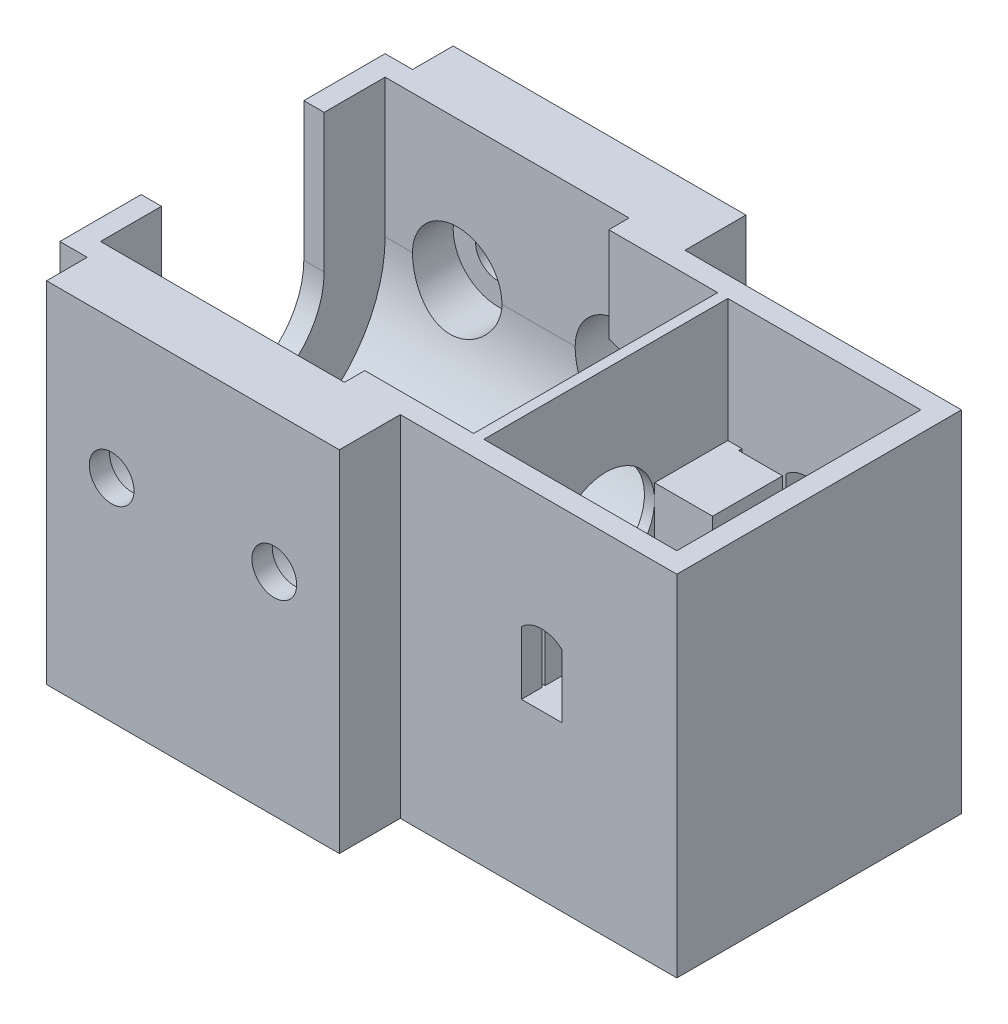
SolidWorks part; units mm, degrees
ref_plane "Front Plane" through (0, 0, 0) normal (0, 0, 1) x (1, 0, 0)
ref_plane "Top Plane" through (0, 0, 0) normal (0, 1, 0) x (1, 0, 0)
ref_plane "Right Plane" through (0, 0, 0) normal (1, 0, 0) x (0, 0, -1)
sketch "Sketch1" plane through (0, 0, 0) normal (0, 0, 1) x (1, 0, 0)
  line L1 (-76.2, -50.8) -> (40.64, -50.8)
  line L2 (-76.2, -50.8) -> (-76.2, 0)
  line L3 (-76.2, 0) -> (40.64, 0)
  line L4 (40.64, -50.8) -> (40.64, 0)
  line L5 (-76.2, -50.8) -> (40.64, 0) construction
  line L6 (-76.2, 0) -> (40.64, -50.8) construction
  point P0 (0, 0)
  dimension "D1" = 116.84
  dimension "D2" = 50.8
  dimension "D3" = 76.2
extrude "Boss-Extrude1" add sketch "Sketch1" along normal mid plane 63.5
sketch "Sketch2" plane through (0, 0, 0) normal (0, 0, 1) x (1, 0, 0)
  line L0 (-152.4829, -25.4) -> (6.8382, -25.4) construction
  line L1 (-49.3609, -3.175) -> (-49.3609, -12.7)
  line L2 (40.64, 0) -> (-76.2, 0) construction
  line L3 (40.64, 0) -> (-76.2, 0) construction
  line L4 (-11.2609, -3.175) -> (-11.2609, -6.35)
  line L5 (-11.2609, -25.4) -> (-11.2609, -3.175) construction
  line L6 (-128.4172, -25.4) -> (-157.8092, -25.4)
  line L7 (6.8382, -25.4) -> (40.64, -25.4)
  line L8 (-607.3619, -25.4) -> (6.8382, -25.4) construction
  line L9 (-49.3609, -3.175) -> (-11.2609, -3.175)
  line L10 (6.8382, -25.4) -> (-128.4172, -25.4)
  line L11 (-11.2609, -6.35) -> (5.7391, -6.35)
  line L12 (5.7391, -6.35) -> (5.7391, -17.78)
  line L13 (5.7391, -17.78) -> (23.7391, -17.78)
  line L14 (-49.3609, -12.7) -> (-220.2024, -12.7)
  line L15 (-220.2024, -12.7) -> (-220.2024, -25.4)
  line L16 (-220.2024, -25.4) -> (-157.8092, -25.4)
  line L17 (23.7391, -17.78) -> (23.7391, -25.4) construction
  line L18 (23.7391, -17.78) -> (40.64, -17.78)
  line L19 (40.64, -50.8) -> (40.64, 0) construction
  line L20 (40.64, -17.78) -> (40.64, -25.4)
  line L21 (-76.2, 0) -> (-76.2, -50.8) construction
  point P23 (-11.2609, -25.4)
  dimension "D1" = 22.225
  dimension "D2" = 38.1
  dimension "D3" = 25.4
  dimension "D4" = 35
  dimension "D5" = 7.62
  dimension "D6" = 3.175
  dimension "D7" = 26.8391
  dimension "D8" = 18
  dimension "D9" = 12.7
revolve "Cut-Revolve1" cut sketch "Sketch2" angle 360 about L0
sketch "Sketch38" plane through (40.64, 0, 0) normal (1, 0, 0) x (0, 0, -1)
  line L1 (-10, -35.4) -> (10, -35.4)
  line L2 (-10, -35.4) -> (-10, -15.4)
  line L3 (-10, -15.4) -> (10, -15.4)
  line L4 (10, -35.4) -> (10, -15.4)
  line L5 (-10, -35.4) -> (10, -15.4) construction
  line L6 (-10, -15.4) -> (10, -35.4) construction
  point P0 (0, -25.4)
  point P1 (0, -25.4)
  dimension "D1" = 20
  dimension "D2" = 20
extrude "Cut-Extrude33" cut sketch "Sketch38" against normal offset from surface (33.3134 mm away) 1.5875 up to face at (5.7391, -44.45, 0)
sketch "Sketch37" plane through (40.64, 0, 0) normal (1, 0, 0) x (0, 0, -1)
  line L0 (31.75, -50.8) -> (31.75, 0) construction
  line L1 (-31.75, 0) -> (31.75, 0)
  line L2 (-31.75, 0) -> (-31.75, -25.4)
  line L3 (-31.75, -25.4) -> (31.75, -25.4)
  line L4 (31.75, 0) -> (31.75, -25.4)
  line L5 (10, -35.4) -> (10, -15.4) construction
  point P7 (0, -25.4)
  point P11 (0, 0)
  point P14 (10, -25.4)
extrude "Cut-Extrude32" cut sketch "Sketch37" against normal through all
sketch "Sketch39" plane through (0, -25.4, 0) normal (0, 1, 0) x (1, 0, 0)
  line L10 (-76.2, 12.7) -> (-49.3609, 12.7)
  line L11 (-49.3609, 12.7) -> (-49.3609, 22.225)
  line L12 (-49.3609, 22.225) -> (-11.2609, 22.225)
  line L13 (-11.2609, 22.225) -> (-11.2609, 19.05)
  line L14 (-11.2609, 19.05) -> (5.7391, 19.05)
  line L15 (5.7391, 19.05) -> (5.7391, 7.62)
  line L16 (5.7391, 19.05) -> (5.7391, 7.62)
  line L17 (40.64, 10) -> (40.64, 31.75)
  line L18 (40.64, 31.75) -> (-76.2, 31.75)
  line L19 (-76.2, 31.75) -> (-76.2, 12.7)
  line L20 (-76.2, 12.7) -> (-49.3609, 12.7)
  line L21 (-49.3609, 12.7) -> (-49.3609, 22.225)
  line L22 (-49.3609, 22.225) -> (-11.2609, 22.225)
  line L23 (-11.2609, 22.225) -> (-11.2609, 19.05)
  line L24 (-11.2609, 19.05) -> (5.7391, 19.05)
  line L25 (7.3266, 10) -> (40.64, 10)
  line L26 (7.3266, 10) -> (40.64, 10)
  line L27 (40.64, 10) -> (40.64, 31.75)
  line L28 (40.64, 31.75) -> (-76.2, 31.75)
  line L29 (-76.2, 31.75) -> (-76.2, 12.7)
  line L30 (-49.3609, -12.7) -> (-76.2, -12.7)
  line L31 (-76.2, -12.7) -> (-76.2, -31.75)
  line L32 (-76.2, -31.75) -> (40.64, -31.75)
  line L33 (40.64, -31.75) -> (40.64, -10)
  line L34 (40.64, -10) -> (7.3266, -10)
  line L35 (40.64, -10) -> (7.3266, -10)
  line L36 (5.7391, -19.05) -> (-11.2609, -19.05)
  line L37 (-11.2609, -19.05) -> (-11.2609, -22.225)
  line L38 (-11.2609, -22.225) -> (-49.3609, -22.225)
  line L39 (-49.3609, -22.225) -> (-49.3609, -12.7)
  line L40 (-49.3609, -12.7) -> (-76.2, -12.7)
  line L41 (-76.2, -12.7) -> (-76.2, -31.75)
  line L42 (-76.2, -31.75) -> (40.64, -31.75)
  line L43 (40.64, -31.75) -> (40.64, -10)
  line L44 (5.7391, -7.62) -> (5.7391, -19.05)
  line L45 (5.7391, -7.62) -> (5.7391, -19.05)
  line L46 (5.7391, -19.05) -> (-11.2609, -19.05)
  line L47 (-11.2609, -19.05) -> (-11.2609, -22.225)
  line L48 (-11.2609, -22.225) -> (-49.3609, -22.225)
  line L49 (-49.3609, -22.225) -> (-49.3609, -12.7)
  line L52 (5.7391, 7.62) -> (7.3266, 7.62)
  line L53 (5.7391, 7.62) -> (7.3266, 7.62)
  line L54 (7.3266, 7.62) -> (7.3266, 10)
  line L55 (7.3266, 7.62) -> (7.3266, 10)
  line L56 (7.3266, -10) -> (7.3266, -7.62)
  line L57 (7.3266, -10) -> (7.3266, -7.62)
  line L58 (7.3266, -7.62) -> (5.7391, -7.62)
  line L59 (7.3266, -7.62) -> (5.7391, -7.62)
  dimension "D1" = 0
  dimension "D2" = 0
extrude "Boss-Extrude5" add sketch "Sketch39" along normal blind 25.4
sketch "Sketch40" plane through (0, 0, 0) normal (0, 1, 0) x (1, 0, 0)
  line L0 (7.3266, 10) -> (40.64, 10) construction
  line L1 (23.7391, 10) -> (40.64, 10)
  line L2 (23.7391, 10) -> (23.7391, -10)
  line L3 (23.7391, -10) -> (40.64, -10)
  line L4 (40.64, 10) -> (40.64, -10)
  line L6 (-11.2609, 22.225) -> (-11.2609, 19.05) construction
  dimension "D1" = 35
extrude "Boss-Extrude6" add sketch "Sketch40" against normal up to next
sketch "Sketch41" plane through (0, 0, 0) normal (0, 1, 0) x (1, 0, 0)
  line L2 (-76.2, 12.7) -> (-76.2, -12.7) construction
  circle A0 centre (-57.15, 0) radius 3.1134
  circle A1 centre (-31.75, 0) radius 3.1134
  circle A2 centre (-6.35, 0) radius 3.1134
  dimension "D1" = 19.05
extrude "Cut-Extrude34" cut sketch "Sketch41" against normal through all
ref_plane "Plane_Mid" through (0, -25.4, 0) normal (0, 1, 0) x (1, 0, 0)
ref_axis "Axis1" through (7.3266, -25.4, 0) along (-1, 0, 0)
sketch "Sketch42" plane through (0, 0, 0) normal (0, 0, 1) x (1, 0, 0)
  line L0 (1.7462, -25.4) -> (-1.7462, -25.4) construction
  line L1 (-76.2, 0) -> (-76.2, -25.4) construction
  circle A0 centre (-38.1, -25.4) radius 3.4925
  circle A1 centre (-12.7, -25.4) radius 3.4925
  dimension "D1" = 6.985
  dimension "D2" = 38.1
extrude "Cut-Extrude35" cut sketch "Sketch42" against normal through all both and the other way through all
sketch "Sketch43" plane through (0, 0, 0) normal (0, 0, 1) x (1, 0, 0)
  circle A0 centre (-38.1, -25.4) radius 6.985
  circle A1 centre (-12.7, -25.4) radius 6.985
  dimension "D1" = 13.97
extrude "Cut-Extrude36" cut sketch "Sketch43" against normal offset from surface (28.575 mm away) 3.175 up to face at (-9.2075, -25.4, -31.75)
extrude "Cut-Extrude37" cut sketch "Sketch43<2>" along normal offset from surface (28.575 mm away) 3.175 up to face at (-9.2075, -25.4, 31.75)
sketch "Sketch43<2>" plane through (0, 0, 0) normal (0, 0, 1) x (1, 0, 0) same geometry as "Sketch43"
sketch "Sketch44" plane through (0, 0, 0) normal (0, 1, 0) x (1, 0, 0)
  line L0 (5.7391, -19.05) -> (-11.2609, -19.05) construction
  line L1 (7.3266, 19.05) -> (23.2391, 19.05)
  line L2 (7.3266, 19.05) -> (7.3266, -19.05)
  line L3 (7.3266, -19.05) -> (23.2391, -19.05)
  line L4 (23.2391, 19.05) -> (23.2391, -19.05)
  line L5 (-11.2609, 19.05) -> (5.7391, 19.05) construction
  line L6 (7.3266, 7.62) -> (7.3266, 10) construction
  line L7 (23.7391, 10) -> (23.7391, -10) construction
  dimension "D1" = 0.5
extrude "Cut-Extrude38" cut sketch "Sketch44" against normal up to surface (35.4 mm away) up to face at (15.5329, -35.4, 0)
sketch "Sketch45" plane through (0, 0, 0) normal (0, 0, 1) x (1, 0, 0)
  line L0 (40.64, 0) -> (-76.2, 0) construction
  line L2 (37.465, 0) -> (23.2391, 0)
  line L4 (37.465, 0) -> (37.465, -15.4)
  line L5 (37.465, -15.4) -> (23.2391, -15.4)
  line L8 (23.2391, 0) -> (23.2391, -15.4)
  line L9 (40.64, -50.8) -> (40.64, 0) construction
  line L10 (23.2391, -35.4) -> (23.2391, 0) construction
  line L11 (-5.715, -25.4) -> (5.7391, -25.4) construction
  dimension "D1" = 3.175
  dimension "D2" = 10
extrude "Cut-Extrude39" cut sketch "Sketch45" against normal up to surface and the other way up to surface up to face at (15.2828, -17.7, -19.05) other way up to face at (15.2828, -17.7, 19.05)
sketch "Sketch46" plane through (0, 0, 0) normal (0, 1, 0) x (1, 0, 0)
  line L0 (-11.2609, 19.05) -> (5.7391, 19.05) construction
  line L1 (40.64, 31.75) -> (-2.54, 31.75)
  line L2 (40.64, 31.75) -> (40.64, 22.225)
  line L3 (40.64, 22.225) -> (-2.54, 22.225)
  line L4 (-2.54, 31.75) -> (-2.54, 22.225)
  line L5 (-76.2, 0) -> (40.64, 0) construction
  line L6 (-76.2, 12.7) -> (-76.2, -12.7) construction
  line L7 (40.64, -31.75) -> (40.64, 31.75) construction
  line L8 (40.64, -31.75) -> (40.64, -22.225)
  line L9 (40.64, -22.225) -> (-2.54, -22.225)
  line L10 (40.64, -31.75) -> (-2.54, -31.75)
  line L11 (-2.54, -31.75) -> (-2.54, -22.225)
  line L12 (-49.3609, 22.225) -> (-11.2609, 22.225) construction
  line L13 (-76.2, 31.75) -> (-48.26, 31.75)
  line L14 (-76.2, 31.75) -> (-76.2, 25.4)
  line L15 (-76.2, 25.4) -> (-48.26, 25.4)
  line L16 (-48.26, 31.75) -> (-48.26, 25.4)
  line L17 (-48.26, -31.75) -> (-48.26, -25.4)
  line L18 (-76.2, -25.4) -> (-48.26, -25.4)
  line L19 (-76.2, -31.75) -> (-76.2, -25.4)
  line L20 (-76.2, -31.75) -> (-48.26, -31.75)
  dimension "D1" = 3.175
  dimension "D2" = 3.175
  dimension "D3" = 3.175
  dimension "D4" = 3.175
extrude "Cut-Extrude40" cut sketch "Sketch46" against normal through all
sketch "Sketch49" plane through (0, 0, 0) normal (0, 1, 0) x (1, 0, 0)
  line L0 (-48.26, -25.4) -> (-76.2, -25.4) construction
  line L1 (-76.2, 25.4) -> (-52.5359, 25.4)
  line L2 (-76.2, 25.4) -> (-76.2, -25.4)
  line L3 (-76.2, -25.4) -> (-52.5359, -25.4)
  line L4 (-52.5359, 25.4) -> (-52.5359, -25.4)
  line L5 (-49.3609, -22.225) -> (-49.3609, 22.225) construction
  dimension "D1" = 3.175
extrude "Cut-Extrude42" cut sketch "Sketch49" against normal through all
sketch "Sketch50" plane through (0, 0, 0) normal (0, 1, 0) x (1, 0, 0)
  line L0 (-2.54, 22.225) -> (40.64, 22.225) construction
  line L1 (22.9851, 20.701) -> (23.2391, 20.701)
  line L2 (22.9851, 20.701) -> (22.9851, 22.225)
  line L3 (22.9851, 22.225) -> (23.2391, 22.225)
  line L4 (23.2391, 20.701) -> (23.2391, 22.225)
  line L5 (23.1121, 22.225) -> (23.1121, 20.701) construction
  line L6 (22.9851, 21.463) -> (23.2391, 21.463) construction
  line L8 (23.2391, 10) -> (23.2391, 19.05) construction
  line L9 (21.4611, 20.701) -> (21.7151, 20.701)
  line L10 (21.7151, 20.701) -> (21.7151, 22.225)
  line L11 (21.4611, 22.225) -> (21.7151, 22.225)
  line L12 (21.4611, 20.701) -> (21.4611, 22.225)
  line L13 (19.9371, 20.701) -> (20.1911, 20.701)
  line L14 (20.1911, 20.701) -> (20.1911, 22.225)
  line L15 (19.9371, 22.225) -> (20.1911, 22.225)
  line L16 (19.9371, 20.701) -> (19.9371, 22.225)
  line L17 (18.4131, 20.701) -> (18.6671, 20.701)
  line L18 (18.6671, 20.701) -> (18.6671, 22.225)
  line L19 (18.4131, 22.225) -> (18.6671, 22.225)
  line L20 (18.4131, 20.701) -> (18.4131, 22.225)
  line L21 (16.8891, 20.701) -> (17.1431, 20.701)
  line L22 (17.1431, 20.701) -> (17.1431, 22.225)
  line L23 (16.8891, 22.225) -> (17.1431, 22.225)
  line L24 (16.8891, 20.701) -> (16.8891, 22.225)
  line L25 (15.3651, 20.701) -> (15.6191, 20.701)
  line L26 (15.6191, 20.701) -> (15.6191, 22.225)
  line L27 (15.3651, 22.225) -> (15.6191, 22.225)
  line L28 (15.3651, 20.701) -> (15.3651, 22.225)
  line L29 (13.8411, 20.701) -> (14.0951, 20.701)
  line L30 (14.0951, 20.701) -> (14.0951, 22.225)
  line L31 (13.8411, 22.225) -> (14.0951, 22.225)
  line L32 (13.8411, 20.701) -> (13.8411, 22.225)
  line L33 (12.3171, 20.701) -> (12.5711, 20.701)
  line L34 (12.5711, 20.701) -> (12.5711, 22.225)
  line L35 (12.3171, 22.225) -> (12.5711, 22.225)
  line L36 (12.3171, 20.701) -> (12.3171, 22.225)
  line L37 (10.7931, 20.701) -> (11.0471, 20.701)
  line L38 (11.0471, 20.701) -> (11.0471, 22.225)
  line L39 (10.7931, 22.225) -> (11.0471, 22.225)
  line L40 (10.7931, 20.701) -> (10.7931, 22.225)
  line L41 (9.2691, 20.701) -> (9.5231, 20.701)
  line L42 (9.5231, 20.701) -> (9.5231, 22.225)
  line L43 (9.2691, 22.225) -> (9.5231, 22.225)
  line L44 (9.2691, 20.701) -> (9.2691, 22.225)
  point P0 (23.1121, 21.463)
  dimension "D1" = 0.254
  dimension "D2" = 1.524
  dimension "D3" = 10
extrude "Cut-Extrude43" cut sketch "Sketch50" against normal blind 2.54
sketch "Sketch52" plane through (23.7391, 0, 0) normal (-1, 0, 0) x (0, 0, 1)
  circle A0 centre (0, -25.4) radius 0.3175
  dimension "D1" = 0.635
extrude "Cut-Extrude45" cut sketch "Sketch52" against normal blind 0.0508
sketch "Sketch53" plane through (23.7391, 0, 0) normal (-1, 0, 0) x (0, 0, 1)
  circle A0 centre (0, -25.4) radius 2
  dimension "D1" = 4
extrude "Cut-Extrude46" cut sketch "Sketch53" against normal blind 0.0254
sketch "Sketch54" plane through (0, -35.4, 0) normal (0, 1, 0) x (1, 0, 0)
  line L0 (23.2391, 10) -> (23.2391, -10)
  line L8 (23.7391, 10) -> (23.2391, 10)
  line L9 (23.2391, 10) -> (23.2391, 19.05)
  line L10 (23.2391, 19.05) -> (7.3266, 19.05)
  line L11 (7.3266, 19.05) -> (7.3266, -19.05)
  line L12 (7.3266, -19.05) -> (23.2391, -19.05)
  line L13 (23.2391, -19.05) -> (23.2391, -10)
  line L14 (23.2391, -10) -> (23.7391, -10)
  line L15 (23.7391, -10) -> (23.7391, 10)
  line L17 (23.2391, 10) -> (23.2391, 19.05)
  line L18 (23.2391, 19.05) -> (7.3266, 19.05)
  line L19 (7.3266, 19.05) -> (7.3266, -19.05)
  line L20 (7.3266, -19.05) -> (23.2391, -19.05)
  line L21 (23.2391, -19.05) -> (23.2391, -10)
  dimension "D1" = 0
extrude "Boss-Extrude7" add sketch "Sketch54" along normal blind 2.54
sketch "Sketch55" plane through (0, -32.86, 0) normal (0, 1, 0) x (1, 0, 0)
  line L0 (23.2391, -19.05) -> (23.2391, -10) construction
  line L1 (23.2391, 10) -> (7.3266, 10)
  line L2 (23.2391, 10) -> (23.2391, 19.05)
  line L3 (23.2391, 19.05) -> (7.3266, 19.05)
  line L4 (7.3266, 10) -> (7.3266, 19.05)
  line L5 (23.2391, 10) -> (7.3266, 19.05) construction
  line L6 (23.2391, 19.05) -> (7.3266, 10) construction
  line L7 (7.3266, -19.05) -> (23.2391, -19.05)
  line L8 (7.3266, -19.05) -> (7.3266, -10)
  line L9 (7.3266, -10) -> (23.2391, -10)
  line L10 (23.2391, -19.05) -> (23.2391, -10)
  line L11 (7.3266, -19.05) -> (23.2391, -10) construction
  line L12 (7.3266, -10) -> (23.2391, -19.05) construction
  point P4 (15.2828, 14.525)
  point P11 (15.2828, -14.525)
extrude "Boss-Extrude8" add sketch "Sketch55" along normal up to surface (17.46 mm away) up to face at (26.9206, -15.4, 0)
sketch "Sketch57" plane through (0, -15.4, 0) normal (0, 1, 0) x (1, 0, 0)
  line L8 (23.7391, -10) -> (7.3266, -10)
  line L9 (7.3266, -10) -> (7.3266, -19.05)
  line L10 (7.3266, -19.05) -> (37.465, -19.05)
  line L11 (37.465, -19.05) -> (37.465, 19.05)
  line L12 (37.465, 19.05) -> (7.3266, 19.05)
  line L13 (23.7391, -10) -> (7.3266, -10)
  line L14 (7.3266, 19.05) -> (7.3266, 10)
  line L15 (23.7391, 10) -> (23.7391, -10)
  line L16 (7.3266, 19.05) -> (7.3266, 10)
  line L17 (7.3266, -10) -> (7.3266, -19.05)
  line L18 (7.3266, -19.05) -> (37.465, -19.05)
  line L19 (37.465, -19.05) -> (37.465, 19.05)
  line L20 (37.465, 19.05) -> (7.3266, 19.05)
  line L21 (7.3266, 10) -> (23.7391, 10)
  line L22 (7.3266, 10) -> (23.7391, 10)
  line L23 (23.7391, 10) -> (23.7391, -10)
  dimension "D1" = 0
extrude "Cut-Extrude47" cut sketch "Sketch57" against normal blind 7.62
sketch "Sketch58" plane through (0, -50.8, 0) normal (0, -1, 0) x (1, 0, 0)
  line L12 (-48.26, 25.4) -> (-52.5359, 25.4)
  line L13 (-52.5359, 25.4) -> (-52.5359, -25.4)
  line L14 (-52.5359, -25.4) -> (-48.26, -25.4)
  line L15 (-48.26, -25.4) -> (-48.26, -31.75)
  line L16 (-48.26, -31.75) -> (-2.54, -31.75)
  line L17 (-2.54, -31.75) -> (-2.54, -22.225)
  line L18 (-2.54, -22.225) -> (40.64, -22.225)
  line L19 (40.64, -22.225) -> (40.64, 22.225)
  line L20 (40.64, 22.225) -> (-2.54, 22.225)
  line L21 (-2.54, 22.225) -> (-2.54, 31.75)
  line L22 (-2.54, 31.75) -> (-48.26, 31.75)
  line L23 (-48.26, 31.75) -> (-48.26, 25.4)
  line L24 (-48.26, 25.4) -> (-52.5359, 25.4)
  line L25 (-52.5359, 25.4) -> (-52.5359, -25.4)
  line L26 (-52.5359, -25.4) -> (-48.26, -25.4)
  line L27 (-48.26, -25.4) -> (-48.26, -31.75)
  line L28 (-48.26, -31.75) -> (-2.54, -31.75)
  line L29 (-2.54, -31.75) -> (-2.54, -22.225)
  line L30 (-2.54, -22.225) -> (40.64, -22.225)
  line L31 (40.64, -22.225) -> (40.64, 22.225)
  line L32 (40.64, 22.225) -> (-2.54, 22.225)
  line L33 (-2.54, 22.225) -> (-2.54, 31.75)
  line L34 (-2.54, 31.75) -> (-48.26, 31.75)
  line L35 (-48.26, 31.75) -> (-48.26, 25.4)
  circle A0 centre (-31.75, 0) radius 3.1134
  circle A1 centre (-6.35, 0) radius 3.1134
  circle A2 centre (-6.35, 0) radius 3.1134 construction
  circle A3 centre (-31.75, 0) radius 3.1134 construction
  dimension "D1" = 0
extrude "Boss-Extrude10" add sketch "Sketch58" along normal blind 7.62
sketch "Sketch59" plane through (0, -35.4, 0) normal (0, 1, 0) x (1, 0, 0)
  line L4 (23.2391, 10) -> (23.2391, -10)
  line L5 (23.2391, -10) -> (23.7391, -10)
  line L6 (23.7391, -10) -> (23.7391, 10)
  line L7 (23.7391, 10) -> (23.2391, 10)
  line L8 (23.2391, 10) -> (23.2391, -10)
  line L9 (23.2391, -10) -> (23.7391, -10)
  line L10 (23.7391, -10) -> (23.7391, 10)
  line L11 (23.7391, 10) -> (23.2391, 10)
  dimension "D1" = 0
extrude "Cut-Extrude48" cut sketch "Sketch59" against normal blind 7.62
sketch "Sketch51" plane through (0, -23.02, 0) normal (0, 1, 0) x (1, 0, 0)
  line L0 (25.098, 0.254) -> (26.1082, 0.254)
  line L1 (24.59, 2.54) -> (25.098, 2.54)
  line L2 (24.59, 2.54) -> (24.59, 0.254)
  line L3 (24.59, -2.54) -> (25.098, -2.54)
  line L4 (25.098, 2.54) -> (25.098, 0.254)
  line L5 (29.6527, -0.254) -> (30.6629, -0.254)
  line L6 (25.098, -0.254) -> (25.098, -2.54)
  line L7 (26.6162, 2.54) -> (26.6162, 0.254)
  line L8 (26.1082, 2.54) -> (26.6162, 2.54)
  line L9 (26.1082, 2.54) -> (26.1082, 0.254)
  line L10 (26.1082, -2.54) -> (26.6162, -2.54)
  line L11 (28.1344, 2.54) -> (28.1344, 0.254)
  line L12 (27.6264, 2.54) -> (28.1344, 2.54)
  line L13 (27.6264, 2.54) -> (27.6264, 0.254)
  line L14 (27.6264, -2.54) -> (28.1344, -2.54)
  line L15 (29.6527, 2.54) -> (29.6527, 0.254)
  line L16 (29.1447, 2.54) -> (29.6527, 2.54)
  line L17 (29.1447, 2.54) -> (29.1447, 0.254)
  line L18 (29.1447, -2.54) -> (29.6527, -2.54)
  line L19 (31.1709, 2.54) -> (31.1709, 0.254)
  line L20 (30.6629, 2.54) -> (31.1709, 2.54)
  line L21 (30.6629, 2.54) -> (30.6629, 0.254)
  line L22 (30.6629, -2.54) -> (31.1709, -2.54)
  line L23 (32.6891, 2.54) -> (32.6891, 0.254)
  line L24 (32.1811, 2.54) -> (32.6891, 2.54)
  line L25 (32.1811, 2.54) -> (32.1811, 0.254)
  line L26 (32.1811, -2.54) -> (32.6891, -2.54)
  line L27 (34.2073, 2.54) -> (34.2073, 0.254)
  line L28 (33.6993, 2.54) -> (34.2073, 2.54)
  line L29 (33.6993, 2.54) -> (33.6993, 0.254)
  line L30 (33.6993, -2.54) -> (34.2073, -2.54)
  line L31 (35.7255, 2.54) -> (35.7255, 0.254)
  line L32 (35.2175, 2.54) -> (35.7255, 2.54)
  line L33 (35.2175, 2.54) -> (35.2175, 0.254)
  line L34 (35.2175, -2.54) -> (35.7255, -2.54)
  line L35 (35.258, 2.5876) -> (24.581, 2.5876) construction
  line L36 (23.32, 11.7754) -> (37.465, 11.7754) construction
  line L37 (25.098, -0.254) -> (26.1082, -0.254)
  line L38 (23.7391, 10) -> (23.7391, -10) construction
  line L39 (37.465, -19.05) -> (37.465, 19.05) construction
  line L40 (23.7391, 0.254) -> (24.59, 0.254)
  line L41 (23.7391, 0.254) -> (23.7391, -0.254)
  line L42 (23.7391, -0.254) -> (24.59, -0.254)
  line L43 (37.465, 0.254) -> (37.465, -0.254)
  line L44 (31.1709, 0.254) -> (32.1811, 0.254)
  line L46 (24.59, -0.254) -> (24.59, -2.54)
  line L47 (26.1082, -0.254) -> (26.1082, -2.54)
  line L48 (26.6162, 0.254) -> (27.6264, 0.254)
  line L49 (26.6162, -0.254) -> (26.6162, -2.54)
  line L51 (26.6162, -0.254) -> (27.6264, -0.254)
  line L52 (27.6264, -0.254) -> (27.6264, -2.54)
  line L53 (28.1344, 0.254) -> (29.1447, 0.254)
  line L54 (28.1344, -0.254) -> (29.1447, -0.254)
  line L55 (28.1344, -0.254) -> (28.1344, -2.54)
  line L56 (29.1447, -0.254) -> (29.1447, -2.54)
  line L57 (29.6527, 0.254) -> (30.6629, 0.254)
  line L58 (31.1709, -0.254) -> (32.1811, -0.254)
  line L61 (29.6527, -0.254) -> (29.6527, -2.54)
  line L62 (30.6629, -0.254) -> (30.6629, -2.54)
  line L63 (31.1709, -0.254) -> (31.1709, -2.54)
  line L64 (32.1811, -0.254) -> (32.1811, -2.54)
  line L65 (32.6891, 0.254) -> (33.6993, 0.254)
  line L66 (32.6891, -0.254) -> (33.6993, -0.254)
  line L67 (32.6891, -0.254) -> (32.6891, -2.54)
  line L68 (33.6993, -0.254) -> (33.6993, -2.54)
  line L69 (34.2073, 0.254) -> (35.2175, 0.254)
  line L70 (34.2073, -0.254) -> (35.2175, -0.254)
  line L71 (34.2073, -0.254) -> (34.2073, -2.54)
  line L72 (35.2175, -0.254) -> (35.2175, -2.54)
  line L73 (35.7255, -0.254) -> (35.7255, -2.54)
  line L74 (35.7255, 0.254) -> (37.465, 0.254)
  line L75 (35.7255, -0.254) -> (37.465, -0.254)
  text T1 "<b>10</b>"
  point P0 (24.717, 0)
  point P51 (30.3925, 0)
  point P52 (23.7391, 0)
  dimension "D1" = 0.508
  dimension "D2" = 5.08
  dimension "D3" = 1.5182
  dimension "D5" = 0.8419
  dimension "D6" = 0.508
  dimension "D4" = 8
extrude "Cut-Extrude44" cut sketch "Sketch51" against normal blind 0.635
sketch "Sketch60" plane through (0, 0, 0) normal (0, 1, 0) x (1, 0, 0)
  line L1 (-60.6783, -40.5295) -> (60.6783, -40.5295)
  line L2 (-60.6783, -40.5295) -> (-60.6783, 40.5295)
  line L3 (-60.6783, 40.5295) -> (60.6783, 40.5295)
  line L4 (60.6783, -40.5295) -> (60.6783, 40.5295)
  line L5 (0, 40.5295) -> (0, -40.5295) construction
  line L6 (-60.6783, 0) -> (60.6783, 0) construction
  point P0 (0, 0)
extrude "Cut-Extrude49" cut sketch "Sketch60" against normal blind 10.16
ref_plane "Plane_Bottom" through (0, -47.625, 0) normal (0, 1, 0) x (1, 0, 0)
ref_plane "Plane_Top" through (0, -3.81, 0) normal (0, 1, 0) x (1, 0, 0)
sketch "Sketch61" plane through (5.7391, 0, 0) normal (-1, 0, 0) x (0, 0, 1)
  circle A0 centre (0, -25.4) radius 7.62
  circle A1 centre (0, -25.4) radius 8.9762
extrude "Boss-Extrude11" add sketch "Sketch61" against normal up to surface (1.5875 mm away) up to face at (7.3266, -22.6511, -10.8884)
sketch "Sketch62" plane through (0, -10.16, 0) normal (0, 1, 0) x (1, 0, 0)
  line L1 (7.3266, 7.62) -> (5.7391, 7.62)
  line L2 (7.3266, 7.62) -> (7.3266, -7.62)
  line L3 (7.3266, -7.62) -> (5.7391, -7.62)
  line L4 (5.7391, 7.62) -> (5.7391, -7.62)
  line L5 (7.3266, 7.62) -> (5.7391, -7.62) construction
  line L6 (7.3266, -7.62) -> (5.7391, 7.62) construction
  point P4 (6.5328, 0)
extrude "Boss-Extrude12" add sketch "Sketch62" against normal up to next
sketch "Sketch64" plane through (0, -10.16, 0) normal (0, 1, 0) x (1, 0, 0)
  line L25 (37.465, 19.05) -> (7.3266, 19.05)
  line L26 (37.465, 19.05) -> (37.465, -19.05)
  line L27 (37.465, -19.05) -> (7.3266, -19.05)
  line L28 (7.3266, 19.05) -> (7.3266, -19.05)
  line L29 (37.465, 19.05) -> (7.3266, -19.05) construction
  line L30 (37.465, -19.05) -> (7.3266, 19.05) construction
  line L48 (-11.2609, 19.05) -> (5.7391, 19.05)
  line L49 (5.7391, 19.05) -> (5.7391, -19.05)
  line L50 (5.7391, -19.05) -> (-11.2609, -19.05)
  line L51 (-11.2609, -19.05) -> (-11.2609, -22.225)
  line L52 (-11.2609, -22.225) -> (-49.3609, -22.225)
  line L53 (-49.3609, -22.225) -> (-49.3609, -12.7)
  line L54 (-49.3609, -12.7) -> (-52.5359, -12.7)
  line L55 (-52.5359, -12.7) -> (-52.5359, -25.4)
  line L56 (-52.5359, -25.4) -> (-48.26, -25.4)
  line L57 (-48.26, -25.4) -> (-48.26, -31.75)
  line L58 (-48.26, -31.75) -> (-2.54, -31.75)
  line L59 (-2.54, -31.75) -> (-2.54, -22.225)
  line L60 (-2.54, -22.225) -> (40.64, -22.225)
  line L61 (40.64, -22.225) -> (40.64, 22.225)
  line L62 (40.64, 22.225) -> (-2.54, 22.225)
  line L63 (-2.54, 22.225) -> (-2.54, 31.75)
  line L64 (-2.54, 31.75) -> (-48.26, 31.75)
  line L65 (-48.26, 31.75) -> (-48.26, 25.4)
  line L66 (-48.26, 25.4) -> (-52.5359, 25.4)
  line L67 (-52.5359, 25.4) -> (-52.5359, 12.7)
  line L68 (-52.5359, 12.7) -> (-49.3609, 12.7)
  line L69 (-49.3609, 12.7) -> (-49.3609, 22.225)
  line L70 (-49.3609, 22.225) -> (-11.2609, 22.225)
  line L71 (-11.2609, 22.225) -> (-11.2609, 19.05)
  line L72 (-11.2609, 19.05) -> (5.7391, 19.05)
  line L73 (5.7391, 19.05) -> (5.7391, -19.05)
  line L74 (5.7391, -19.05) -> (-11.2609, -19.05)
  line L75 (-11.2609, -19.05) -> (-11.2609, -22.225)
  line L76 (-11.2609, -22.225) -> (-49.3609, -22.225)
  line L77 (-49.3609, -22.225) -> (-49.3609, -12.7)
  line L78 (-49.3609, -12.7) -> (-52.5359, -12.7)
  line L79 (-52.5359, -12.7) -> (-52.5359, -25.4)
  line L80 (-52.5359, -25.4) -> (-48.26, -25.4)
  line L81 (-48.26, -25.4) -> (-48.26, -31.75)
  line L82 (-48.26, -31.75) -> (-2.54, -31.75)
  line L83 (-2.54, -31.75) -> (-2.54, -22.225)
  line L84 (-2.54, -22.225) -> (40.64, -22.225)
  line L85 (40.64, -22.225) -> (40.64, 22.225)
  line L86 (40.64, 22.225) -> (-2.54, 22.225)
  line L87 (-2.54, 22.225) -> (-2.54, 31.75)
  line L88 (-2.54, 31.75) -> (-48.26, 31.75)
  line L89 (-48.26, 31.75) -> (-48.26, 25.4)
  line L90 (-48.26, 25.4) -> (-52.5359, 25.4)
  line L91 (-52.5359, 25.4) -> (-52.5359, 12.7)
  line L92 (-52.5359, 12.7) -> (-49.3609, 12.7)
  line L93 (-49.3609, 12.7) -> (-49.3609, 22.225)
  line L94 (-49.3609, 22.225) -> (-11.2609, 22.225)
  line L95 (-11.2609, 22.225) -> (-11.2609, 19.05)
  point P28 (22.3958, 0)
  dimension "D1" = 0
extrude "Boss-Extrude14" add sketch "Sketch64" along normal up to surface (6.35 mm away) up to plane "Plane_Top"
sketch "Sketch65" plane through (7.3266, 0, 0) normal (1, 0, 0) x (0, 0, -1)
  line L0 (-10, -23.02) -> (-7.62, -23.02)
  line L1 (10, -23.02) -> (7.62, -23.02)
  line L2 (-7.62, -32.86) -> (-7.62, -23.02)
  line L3 (7.62, -32.86) -> (7.62, -23.02)
  line L6 (-10, -23.02) -> (-10, -32.86)
  line L7 (-10, -32.86) -> (-7.62, -32.86)
  line L8 (7.62, -32.86) -> (10, -32.86)
  line L28 (10, -32.86) -> (10, -23.02)
  point P12 (8.81, -23.02)
extrude "Boss-Extrude16" add sketch "Sketch65" along normal up to next
sketch "Sketch66" plane through (0, -23.02, 0) normal (0, 1, 0) x (1, 0, 0)
  line L0 (23.2391, -7.62) -> (23.2391, 7.62) construction
  line L1 (23.7391, 10) -> (23.2391, 10)
  line L2 (23.7391, 10) -> (23.7391, -10)
  line L3 (23.7391, -10) -> (23.2391, -10)
  line L4 (23.2391, 10) -> (23.2391, -10)
  line L5 (23.7391, 10) -> (23.2391, -10) construction
  line L6 (23.7391, -10) -> (23.2391, 10) construction
  line L9 (7.3266, 0) -> (5.7391, 0) construction
  line L10 (23.7391, -0.254) -> (23.7391, -7.62) construction
  point P4 (23.4891, 0)
  dimension "D1" = 20
extrude "Cut-Extrude50" cut sketch "Sketch66" against normal up to surface (20 mm away) up to face at (23.4891, -43.02, 0)
sketch "Sketch67" plane through (0, -23.02, 0) normal (0, 1, 0) x (1, 0, 0)
  line L0 (23.2391, 7.62) -> (7.3266, 7.62) construction
  line L1 (22.7311, 7.62) -> (16.3811, 7.62)
  line L2 (22.7311, 7.62) -> (22.7311, 18.542)
  line L3 (37.465, 19.05) -> (7.3266, 19.05) construction
  line L4 (16.3811, 7.62) -> (16.3811, 18.542)
  line L5 (22.7311, 18.542) -> (29.5891, 18.542)
  line L6 (9.5231, 19.05) -> (29.5891, 19.05)
  line L7 (9.5231, 19.05) -> (9.5231, 18.542)
  line L8 (9.5231, 18.542) -> (16.3811, 18.542)
  line L9 (29.5891, 19.05) -> (29.5891, 18.542)
  point P10 (19.5561, 7.62)
  point P12 (19.5561, 19.05)
  dimension "D1" = 0.508
  dimension "D2" = 0.508
  dimension "D3" = 20.066
  dimension "D4" = 6.35
extrude "Cut-Extrude51" cut sketch "Sketch67" against normal up to surface (9.84 mm away) up to face at (12.6308, -32.86, 0)
ref_plane "Plane Laser Access" through (19.5561, 0, 0) normal (-1, 0, 0) x (0, 0, 1)
ref_axis "Axis Laser Access" through (19.5561, -25.4, -21.7488) along (0, 0, 1)
sketch "Sketch69" plane through (0, 0, -19.05) normal (0, 0, 1) x (1, 0, 0)
  line L0 (9.5231, -32.86) -> (29.5891, -32.86) construction
  line L1 (16.3811, -32.86) -> (22.7311, -32.86)
  line L2 (16.3811, -32.86) -> (16.3811, -23.02)
  line L4 (22.7311, -32.86) -> (22.7311, -23.02)
  line L5 (16.3811, -32.86) -> (16.3811, -23.02) construction
  line L6 (22.7311, -32.86) -> (22.7311, -23.02) construction
  line L8 (19.5561, 5.412) -> (19.5561, -5.412) construction
  arc A0 (22.7311, -23.02) -> (16.3811, -23.02) centre (19.5561, -26.3538) ccw
  point P2 (19.5561, -21.75)
  point P11 (0, 0)
  point P12 (22.7311, -24.1883)
  point P13 (19.7366, -21.9011)
  point P16 (0, 0)
  point P19 (0, 0)
  point P20 (19.5561, -21.75)
  point P21 (19.5561, -23.02)
  point P22 (16.3811, -21.7779)
  point P23 (0, 0)
  dimension "D1" = 1.27
extrude "Cut-Extrude53" cut sketch "Sketch69" against normal through all
mirror "Mirror1" about plane through (0, 0, 0) normal (0, 0, 1) of "Cut-Extrude53", "Cut-Extrude51"
